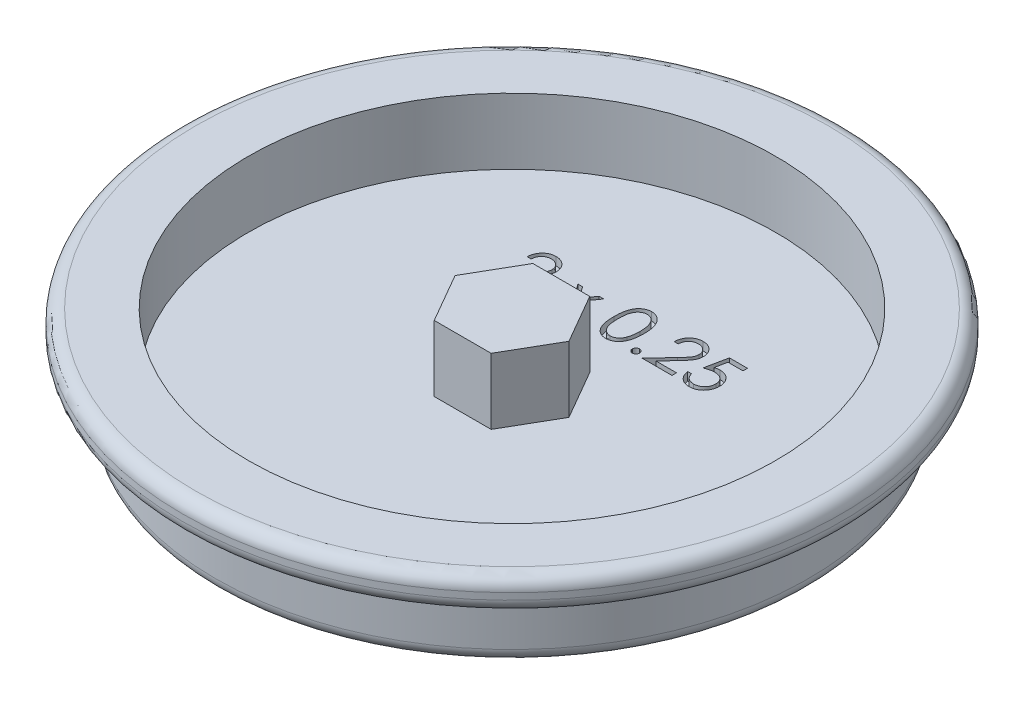
SolidWorks part; units mm, degrees
ref_plane "Front Plane" through (0, 0, 0) normal (0, 0, 1) x (1, 0, 0)
ref_plane "Top Plane" through (0, 0, 0) normal (0, 1, 0) x (1, 0, 0)
ref_plane "Right Plane" through (0, 0, 0) normal (1, 0, 0) x (0, 0, -1)
sketch "Sketch1" plane through (0, 0, 0) normal (0, 0, 1) x (1, 0, 0)
  line L0 (0, 0) -> (27.305, 0)
  line L1 (28.575, 1.27) -> (28.575, 5.08)
  line L2 (29.845, 6.35) -> (30.48, 6.35)
  line L3 (31.75, 7.62) -> (31.75, 8.255)
  line L4 (30.48, 9.525) -> (25.4, 9.525)
  line L5 (25.4, 9.525) -> (25.4, 3.175)
  line L6 (25.4, 3.175) -> (0, 3.175)
  line L7 (0, 3.175) -> (0, 0)
  arc A0 (31.75, 8.255) -> (30.48, 9.525) centre (30.48, 8.255) ccw
  arc A1 (30.48, 6.35) -> (31.75, 7.62) centre (30.48, 7.62) ccw
  arc A2 (28.575, 5.08) -> (29.845, 6.35) centre (29.845, 5.08) cw
  arc A3 (27.305, 0) -> (28.575, 1.27) centre (27.305, 1.27) ccw
  point P3 (0, 1.5875)
  dimension "D7" = 1.27
  dimension "D1" = 3.175
  dimension "D2" = 3.175
  dimension "D3" = 3.175
  dimension "D4" = 6.35
  dimension "D5" = 25.4
  dimension "D6" = 6.35
revolve "Revolve1" add sketch "Sketch1" angle 360 about L7
sketch "Sketch2" plane through (0, 3.175, 0) normal (0, 1, 0) x (1, 0, 0)
  line L1 (2.7423, 4.7498) -> (-2.7423, 4.7498)
  line L2 (-2.7423, 4.7498) -> (-5.4846, 0)
  line L3 (-5.4846, 0) -> (-2.7423, -4.7498)
  line L4 (-2.7423, -4.7498) -> (2.7423, -4.7498)
  line L5 (2.7423, -4.7498) -> (5.4846, 0)
  line L6 (5.4846, 0) -> (2.7423, 4.7498)
  circle A0 centre (0, 0) radius 4.7498 construction
  dimension "D1" = 9.4996
extrude "Boss-Extrude1" add sketch "Sketch2" along normal blind 6.35
sketch "Sketch3" plane through (0, 3.175, 0) normal (0, 1, 0) x (1, 0, 0)
  text T0 "2 x 0.25" font "Century Gothic" height in points 16
extrude "Cut-Extrude1" cut sketch "Sketch3" against normal blind 0.7937
